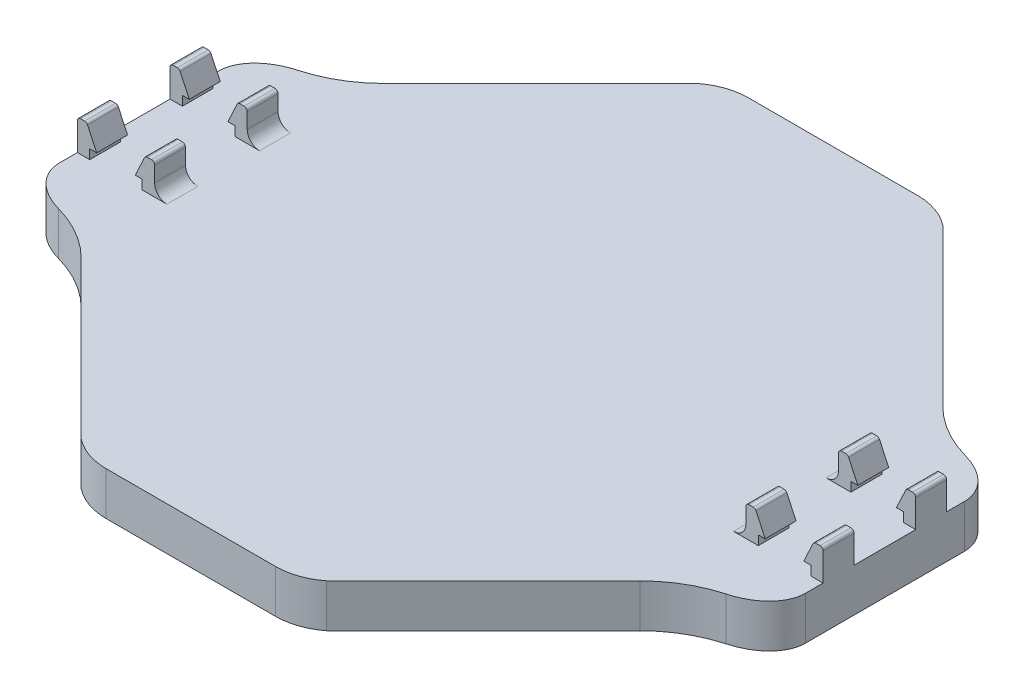
SolidWorks part; units mm, degrees
ref_plane "Front Plane" through (0, 0, 0) normal (0, 0, 1) x (1, 0, 0)
ref_plane "Top Plane" through (0, 0, 0) normal (0, 1, 0) x (1, 0, 0)
ref_plane "Right Plane" through (0, 0, 0) normal (1, 0, 0) x (0, 0, -1)
sketch "Sketch1" plane through (0, 0, 0) normal (0, 1, 0) x (1, 0, 0)
  line L1 (0, 0) -> (99.75, 0)
  line L2 (0, 0) -> (0, 99.75)
  line L3 (0, 99.75) -> (99.75, 99.75)
  line L4 (99.75, 0) -> (99.75, 99.75)
  dimension "D1" = 99.75
  dimension "D2" = 99.75
extrude "Boss-Extrude5" add sketch "Sketch1" along normal blind 7
chamfer "Chamfer2" distance 30 angle 45 4 edges at (0, 3.5, 0) (99.75, 3.5, 0) (0, 3.5, -99.75) (99.75, 3.5, -99.75)
sketch "Sketch6" plane through (0, 0, 0) normal (0, 0, 1) x (1, 0, 0)
  line L1 (30, 7) -> (69.75, 7)
  line L2 (30, 7) -> (30, 0)
  line L3 (30, 0) -> (69.75, 0)
  line L4 (69.75, 7) -> (69.75, 0)
extrude "Boss-Extrude7" add sketch "Sketch6" along normal blind 2.13
sketch "Sketch8" plane through (0, 0, -99.75) normal (0, 0, -1) x (-1, 0, 0)
  line L1 (-30, 7) -> (-69.75, 7)
  line L2 (-30, 7) -> (-30, 0)
  line L3 (-30, 0) -> (-69.75, 0)
  line L4 (-69.75, 7) -> (-69.75, 0)
extrude "Boss-Extrude10" add sketch "Sketch8" along normal blind 2.13
sketch "Sketch12" plane through (0, 0, 0) normal (-1, 0, 0) x (0, 0, 1)
  line L1 (-69.75, 0) -> (-30, 0)
  line L2 (-69.75, 0) -> (-69.75, 7)
  line L3 (-69.75, 7) -> (-30, 7)
  line L4 (-30, 0) -> (-30, 7)
extrude "Boss-Extrude14" add sketch "Sketch12" along normal blind 10.5
sketch "Sketch14" plane through (99.75, 0, 0) normal (1, 0, 0) x (0, 0, -1)
  line L1 (30, 7) -> (69.75, 7)
  line L2 (30, 7) -> (30, 0)
  line L3 (30, 0) -> (69.75, 0)
  line L4 (69.75, 7) -> (69.75, 0)
extrude "Boss-Extrude16" add sketch "Sketch14" along normal blind 10.5
sketch "Sketch15" plane through (0, 7, 0) normal (0, 1, 0) x (1, 0, 0)
  line L0 (0, 30) -> (0, 39.875) construction
  line L1 (0, 44.875) -> (0, 54.875) construction
  line L2 (0, 39.875) -> (2, 39.875)
  line L3 (0, 39.875) -> (0, 44.875)
  line L4 (0, 44.875) -> (2, 44.875)
  line L5 (2, 39.875) -> (2, 44.875)
  line L6 (0, 54.875) -> (2, 54.875)
  line L7 (0, 54.875) -> (0, 59.875)
  line L8 (0, 59.875) -> (2, 59.875)
  line L9 (2, 54.875) -> (2, 59.875)
  line L10 (0, 59.875) -> (0, 69.75) construction
  line L11 (49.875, -2.13) -> (49.875, 101.88) construction
  line L12 (69.75, -2.13) -> (30, -2.13) construction
  line L13 (30, 101.88) -> (69.75, 101.88) construction
  line L14 (0, 30) -> (-8.5, 30) construction
  line L15 (-10.5, 30) -> (0, 30) construction
  line L16 (-8.5, 30) -> (-10.5, 30) construction
  line L17 (-4.25, 30) -> (-4.25, 69.75) construction
  line L18 (-10.5, 69.75) -> (0, 69.75) construction
  line L19 (-10.5, 54.875) -> (-10.5, 59.875)
  line L20 (-8.5, 59.875) -> (-10.5, 59.875)
  line L21 (-8.5, 54.875) -> (-8.5, 59.875)
  line L22 (-8.5, 54.875) -> (-10.5, 54.875)
  line L23 (-10.5, 39.875) -> (-10.5, 44.875)
  line L24 (-8.5, 44.875) -> (-10.5, 44.875)
  line L25 (-8.5, 39.875) -> (-8.5, 44.875)
  line L26 (-8.5, 39.875) -> (-10.5, 39.875)
  line L27 (108.25, 39.875) -> (110.25, 39.875)
  line L28 (108.25, 39.875) -> (108.25, 44.875)
  line L29 (108.25, 44.875) -> (110.25, 44.875)
  line L30 (110.25, 39.875) -> (110.25, 44.875)
  line L31 (108.25, 54.875) -> (110.25, 54.875)
  line L32 (108.25, 54.875) -> (108.25, 59.875)
  line L33 (108.25, 59.875) -> (110.25, 59.875)
  line L34 (110.25, 54.875) -> (110.25, 59.875)
  line L35 (97.75, 54.875) -> (97.75, 59.875)
  line L36 (99.75, 59.875) -> (97.75, 59.875)
  line L37 (99.75, 54.875) -> (99.75, 59.875)
  line L38 (99.75, 54.875) -> (97.75, 54.875)
  line L39 (97.75, 39.875) -> (97.75, 44.875)
  line L40 (99.75, 44.875) -> (97.75, 44.875)
  line L41 (99.75, 39.875) -> (99.75, 44.875)
  line L42 (99.75, 39.875) -> (97.75, 39.875)
  dimension "D1" = 5
  dimension "D2" = 2
  dimension "D3" = 2
  dimension "D4" = 10
extrude "Boss-Extrude17" add sketch "Sketch15" along normal blind 5
fillet "Fillet5" radius 2 4 edges at (2, 7, -57.375) (2, 7, -42.375) (97.75, 7, -57.375) (97.75, 7, -42.375)
sketch "Sketch16" plane through (99.75, 0, 0) normal (1, 0, 0) x (0, 0, -1)
  line L0 (39.875, 7) -> (39.875, 8.52) construction
  line L1 (39.875, 12) -> (39.875, 7) construction
  line L2 (59.875, 12) -> (59.875, 7) construction
  line L3 (39.875, 8.52) -> (44.875, 8.52)
  line L4 (39.875, 8.52) -> (39.875, 12)
  line L5 (39.875, 12) -> (44.875, 12)
  line L6 (44.875, 8.52) -> (44.875, 12)
  line L7 (54.875, 12) -> (59.875, 12)
  line L8 (54.875, 12) -> (54.875, 8.52)
  line L9 (54.875, 8.52) -> (59.875, 8.52)
  line L10 (59.875, 12) -> (59.875, 8.52)
  dimension "D1" = 1.52
extrude "Boss-Extrude18" add sketch "Sketch16" along normal blind 2
sketch "Sketch17" plane through (108.25, 0, 0) normal (-1, 0, 0) x (0, 0, 1)
  line L0 (-59.875, 7) -> (-59.875, 8.52)
  line L1 (-59.875, 12) -> (-59.875, 7) construction
  line L2 (-39.875, 12) -> (-39.875, 7) construction
  line L3 (-59.875, 8.52) -> (-54.875, 8.52)
  line L4 (-59.875, 8.52) -> (-59.875, 12)
  line L5 (-59.875, 12) -> (-54.875, 12)
  line L6 (-54.875, 8.52) -> (-54.875, 12)
  line L7 (-44.875, 12) -> (-39.875, 12)
  line L8 (-44.875, 12) -> (-44.875, 8.52)
  line L9 (-44.875, 8.52) -> (-39.875, 8.52)
  line L10 (-39.875, 12) -> (-39.875, 8.52)
  line M5 (-54.875, 7) -> (-54.875, 12)
  line M6 (-54.875, 12) -> (-59.875, 12)
  line M7 (-59.875, 12) -> (-59.875, 7)
  dimension "D1" = 1.52
extrude "Boss-Extrude19" add sketch "Sketch17" along normal blind 2 contours L3 M7 M5 M6 | L10 L7 L8 L9 region at (108.25, 10.26, -57.375) region at (108.25, 10.26, -42.375)
sketch "Sketch18" plane through (0, 0, 0) normal (-1, 0, 0) x (0, 0, 1)
  line L0 (-59.875, 7) -> (-59.875, 8.52) construction
  line L1 (-59.875, 12) -> (-59.875, 7) construction
  line L2 (-39.875, 12) -> (-39.875, 7) construction
  line L3 (-59.875, 8.52) -> (-54.875, 8.52)
  line L4 (-59.875, 8.52) -> (-59.875, 12)
  line L5 (-59.875, 12) -> (-54.875, 12)
  line L6 (-54.875, 8.52) -> (-54.875, 12)
  line L7 (-44.875, 12) -> (-39.875, 12)
  line L8 (-44.875, 12) -> (-44.875, 8.52)
  line L9 (-44.875, 8.52) -> (-39.875, 8.52)
  line L10 (-39.875, 12) -> (-39.875, 8.52)
  dimension "D1" = 1.52
extrude "Boss-Extrude20" add sketch "Sketch18" along normal blind 2
sketch "Sketch19" plane through (-8.5, 0, 0) normal (1, 0, 0) x (0, 0, -1)
  line L0 (59.875, 7) -> (59.875, 8.52) construction
  line L1 (59.875, 12) -> (59.875, 7) construction
  line L2 (54.875, 12) -> (59.875, 12) construction
  line L3 (59.875, 8.52) -> (54.875, 8.52)
  line L4 (59.875, 8.52) -> (59.875, 12)
  line L5 (59.875, 12) -> (54.875, 12)
  line L6 (54.875, 8.52) -> (54.875, 12)
  line L7 (54.875, 12) -> (54.875, 7) construction
  line L8 (44.875, 12) -> (44.875, 7) construction
  line L9 (39.875, 12) -> (44.875, 12)
  line L10 (39.875, 12) -> (39.875, 8.52)
  line L11 (39.875, 8.52) -> (44.875, 8.52)
  line L12 (44.875, 12) -> (44.875, 8.52)
  dimension "D1" = 1.52
extrude "Boss-Extrude21" add sketch "Sketch19" along normal blind 2
chamfer "Chamfer6" distance 2.5 angle 65 1 edges at (106.25, 12, -42.375) first distance on face at (108.25, 12, -42.375)
chamfer "Chamfer7" distance 2.5 angle 65 7 edges at (-6.5, 12, -42.375) (-6.5, 12, -57.375) (-2, 12, -57.375) (-2, 12, -42.375) (101.75, 12, -42.375) (101.75, 12, -57.375) (106.25, 12, -57.375) first distance on face at (-8.5, 12, -42.375) first distance on face at (-8.5, 12, -57.375) first distance on face at (0, 12, -57.375) first distance on face at (0, 12, -42.375) first distance on face at (99.75, 12, -42.375) first distance on face at (99.75, 12, -57.375) first distance on face at (108.25, 12, -57.375)
fillet "Fillet6" radius 0.5 16 edges at (-10.5, 12, -42.375) (-9, 12, -42.375) (-9, 12, -57.375) (-10.5, 12, -57.375) (2, 12, -57.375) (0.5, 12, -57.375) (2, 12, -42.375) (0.5, 12, -42.375) (97.75, 12, -57.375) (99.25, 12, -57.375) (97.75, 12, -42.375) (99.25, 12, -42.375) (110.25, 12, -42.375) (108.75, 12, -42.375) (110.25, 12, -57.375) (108.75, 12, -57.375)
fillet "Fillet7" radius 10 4 edges at (-10.5, 3.5, -69.75) (-10.5, 3.5, -30) (110.25, 3.5, -69.75) (110.25, 3.5, -30) second distance 7 first distance on face at (-5.25, 3.5, -69.75) first distance on face at (-5.25, 3.5, -30) first distance on face at (105, 3.5, -69.75) first distance on face at (105, 3.5, -30)
fillet "Fillet8" radius 20 4 edges at (0, 3.5, -30) (0, 3.5, -69.75) (99.75, 3.5, -69.75) (99.75, 3.5, -30)
fillet "Fillet9" radius 10 4 edges at (30, 3.5, 2.13) (69.75, 3.5, 2.13) (30, 3.5, -101.88) (69.75, 3.5, -101.88)
equation "\"mountwidth\" = 99.75mm"
equation "\"mountlength\" = 104mm"
equation "\"D1@Sketch1\"=\"mountwidth\""
equation "\"D2@Sketch1\"=\"mountwidth\""
equation "\"framwidth\" = 1.52mm"
equation "\"frameclipwid\" = 8.5mm"
